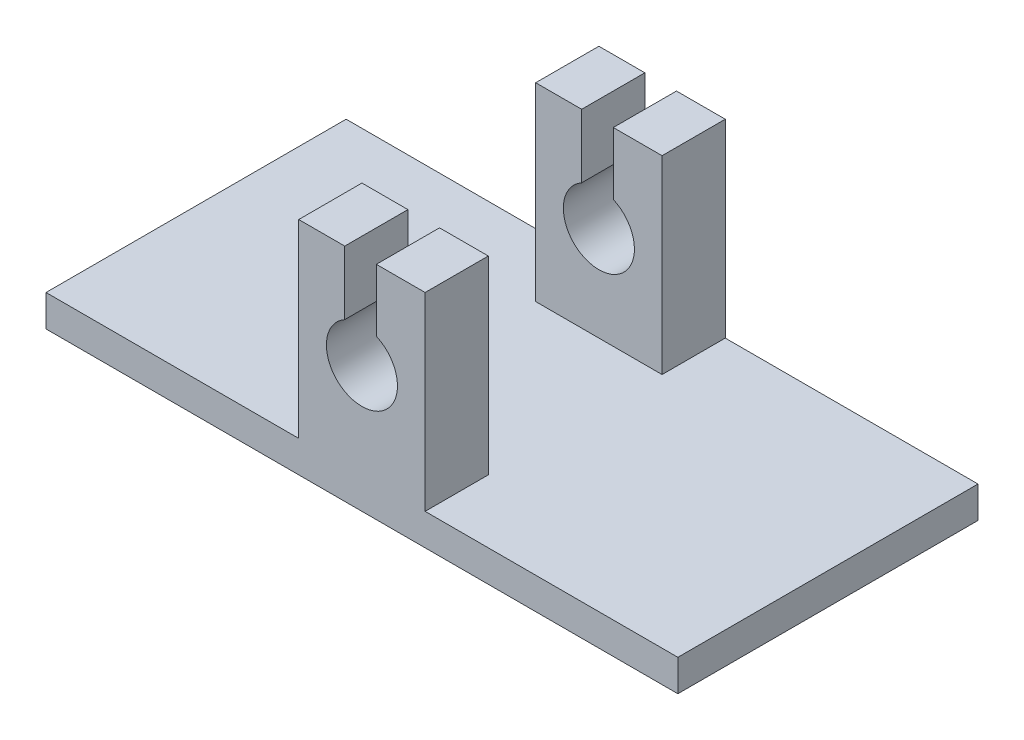
SolidWorks part; units mm, degrees
ref_plane "Front Plane" through (0, 0, 0) normal (0, 0, 1) x (1, 0, 0)
ref_plane "Top Plane" through (0, 0, 0) normal (0, 1, 0) x (1, 0, 0)
ref_plane "Right Plane" through (0, 0, 0) normal (1, 0, 0) x (0, 0, -1)
sketch "Sketch2" plane through (0, 0, 0) normal (0, 1, 0) x (1, 0, 0)
  line L1 (-127, -60.325) -> (127, -60.325)
  line L2 (-127, -60.325) -> (-127, 60.325)
  line L3 (-127, 60.325) -> (127, 60.325)
  line L4 (127, -60.325) -> (127, 60.325)
  line L5 (-127, -60.325) -> (127, 60.325) construction
  line L6 (-127, 60.325) -> (127, -60.325) construction
  point P0 (0, 0)
  dimension "D1" = 120.65
  dimension "D2" = 254
extrude "Boss-Extrude2" add sketch "Sketch2" along normal blind 12.7
sketch "Sketch4" plane through (0, 12.7, 0) normal (0, 1, 0) x (1, 0, 0)
  line L0 (-127, -60.325) -> (0, -60.325) construction
  line L1 (-127, -60.325) -> (127, -60.325) construction
  line L2 (0, -60.325) -> (0, -47.625) construction
  line L3 (0, -47.625) -> (25.4, -47.625) construction
  line L4 (25.4, -47.625) -> (25.4, -34.925) construction
  line L6 (-25.4, -60.325) -> (25.4, -60.325)
  line L7 (-25.4, -60.325) -> (-25.4, -34.925)
  line L8 (-25.4, -34.925) -> (25.4, -34.925)
  line L9 (25.4, -60.325) -> (25.4, -34.925)
  line L10 (-25.4, -60.325) -> (25.4, -34.925) construction
  line L11 (-25.4, -34.925) -> (25.4, -60.325) construction
  dimension "D1" = 12.7
  dimension "D2" = 25.4
  dimension "D3" = 12.7
extrude "Boss-Extrude3" add sketch "Sketch4" along normal blind 76.2
mirror "Mirror1" about plane through (0, 0, 0) normal (0, 0, 1) of "Boss-Extrude3"
sketch "Sketch6" plane through (0, 0, 60.325) normal (0, 0, 1) x (1, 0, 0)
  line L0 (-127, 0) -> (127, 0) construction
  line L1 (-25.4, 88.9) -> (25.4, 88.9) construction
  line L4 (-6.9118, 88.9) -> (5.7882, 88.9)
  line L5 (-6.9118, 88.9) -> (-6.9118, 63.3044)
  line L7 (5.7882, 88.9) -> (5.7882, 63.8625)
  arc A0 (-6.9118, 63.3044) -> (5.7882, 63.8625) centre (0, 50.8) ccw
  point P4 (-6.9118, 88.9)
  dimension "D1" = 28.575
  dimension "D2" = 50.8
  dimension "D3" = 12.7
extrude "Cut-Extrude1" cut sketch "Sketch6" against normal through all
